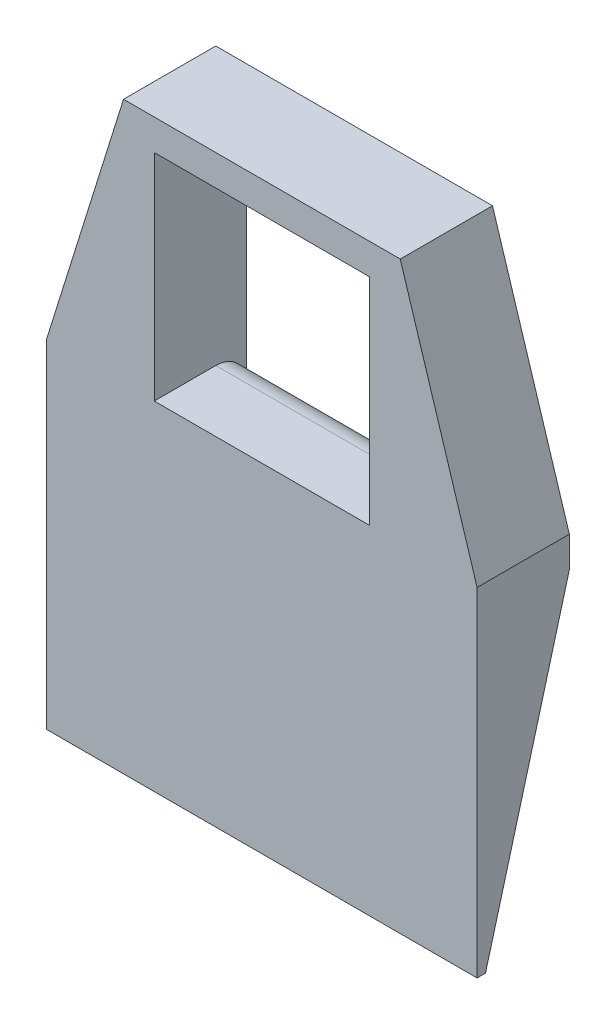
SolidWorks part; units mm, degrees
ref_plane "Front Plane" through (0, 0, 0) normal (0, 0, 1) x (1, 0, 0)
ref_plane "Top Plane" through (0, 0, 0) normal (0, 1, 0) x (1, 0, 0)
ref_plane "Right Plane" through (0, 0, 0) normal (1, 0, 0) x (0, 0, -1)
sketch "Sketch1" plane through (0, 0, 0) normal (0, 1, 0) x (1, 0, 0)
  line L1 (-14, 3) -> (14, 3)
  line L2 (-14, 3) -> (-14, -3)
  line L3 (-14, -3) -> (14, -3)
  line L4 (14, 3) -> (14, -3)
  line L5 (-14, 3) -> (14, -3) construction
  line L6 (-14, -3) -> (14, 3) construction
  point P0 (0, 0)
  dimension "D1" = 28
  dimension "D2" = 6
extrude "Boss-Extrude1" add sketch "Sketch1" along normal blind 2
sketch "Sketch2" plane through (0, 2, 0) normal (0, 1, 0) x (1, 0, 0)
  line L0 (-14, -3) -> (14, -3) construction
  line L1 (-14, 3) -> (-7, 3)
  line L2 (-14, 3) -> (-14, -3)
  line L3 (-14, -3) -> (-7, -3)
  line L4 (-7, 3) -> (-7, -3)
  line L6 (14, 3) -> (7, 3)
  line L7 (14, 3) -> (14, -3)
  line L8 (14, -3) -> (7, -3)
  line L9 (7, 3) -> (7, -3)
  line L10 (-7, 0.5146) -> (7, 0.5146) construction
  line L11 (-7, 0.5146) -> (-7, -0.5146) construction
  line L12 (-7, -0.5146) -> (7, -0.5146) construction
  line L13 (7, 0.5146) -> (7, -0.5146) construction
  line L14 (-7, 0.5146) -> (7, -0.5146) construction
  line L15 (-7, -0.5146) -> (7, 0.5146) construction
  point P12 (0, 0)
  dimension "D1" = 14
extrude "Boss-Extrude2" add sketch "Sketch2" along normal blind 16
sketch "Sketch3" plane through (-7, 0, 0) normal (1, 0, 0) x (0, 0, -1)
  line L0 (3, 18) -> (3, 2) construction
  line L1 (-3, 18) -> (3, 18)
  line L2 (-3, 18) -> (-3, 16)
  line L3 (-3, 16) -> (3, 16)
  line L4 (3, 18) -> (3, 16)
  dimension "D1" = 2
extrude "Boss-Extrude3" add sketch "Sketch3" along normal blind 14
sketch "Sketch4" plane through (0, 0, -3) normal (0, 0, -1) x (-1, 0, 0)
  line L0 (-7, 2) -> (-14, 2) construction
  line L1 (-14, 18) -> (-14, 0) construction
  line L2 (7, 2) -> (14, 2) construction
  line L3 (14, 18) -> (14, 0) construction
  line L4 (-7, 16) -> (-7, 18) construction
  line L5 (-14, 18) -> (14, 18) construction
  line L6 (-7, 18) -> (-9, 18) construction
  line L7 (7, 16) -> (7, 18) construction
  line L8 (7, 18) -> (9, 18) construction
  line L9 (-9, 18) -> (-14, 18)
  line L10 (-14, 18) -> (-14, 2)
  line L11 (-14, 2) -> (-9, 18)
  line L12 (9, 18) -> (14, 18)
  line L13 (14, 18) -> (14, 2)
  line L14 (14, 2) -> (9, 18)
  dimension "D1" = 2
  dimension "D2" = 2
extrude "Cut-Extrude1" cut sketch "Sketch4" against normal through all
sketch "Sketch5" plane through (0, 0, 0) normal (0, -1, 0) x (1, 0, 0)
  line L1 (-14, 3) -> (14, 3)
  line L2 (-14, 3) -> (-14, -3)
  line L3 (-14, -3) -> (14, -3)
  line L4 (14, 3) -> (14, -3)
extrude "Boss-Extrude4" add sketch "Sketch5" along normal blind 22
sketch "Sketch6" plane through (14, 0, 0) normal (1, 0, 0) x (0, 0, -1)
  line L0 (3, 0) -> (-3, -22)
  line L1 (3, 2) -> (3, -22) construction
  line L2 (-3, -22) -> (3, -22)
  line L3 (3, -22) -> (3, 0)
  line L4 (-3, 2) -> (3, 2) construction
  dimension "D1" = 2
extrude "Cut-Extrude2" cut sketch "Sketch6" against normal blind 30
sketch "Sketch7" plane through (14, 0, 0) normal (1, 0, 0) x (0, 0, -1)
  line L0 (-3, -22) -> (-3, -20)
  line L1 (-3, 2) -> (-3, -22) construction
  line L2 (-3, -20) -> (-2.4545, -20)
  line L3 (3, 0) -> (-3, -22) construction
  line L4 (-2.4545, -20) -> (-3, -22)
  dimension "D1" = 2
extrude "Cut-Extrude3" cut sketch "Sketch7" against normal blind 30
fillet "Fillet1" radius 2 1 edges at (0, 2, -3)
